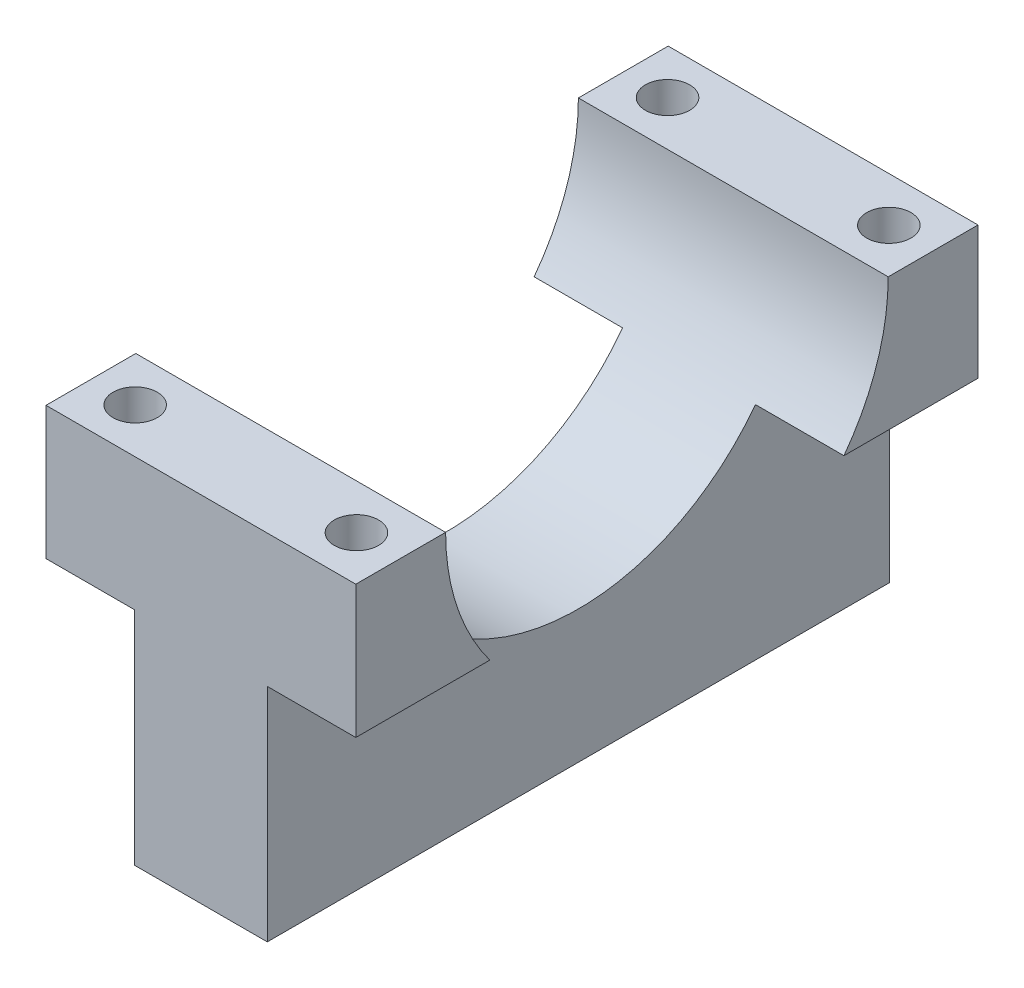
SolidWorks part; units mm, degrees
ref_plane "Front Plane" through (0, 0, 0) normal (0, 0, 1) x (1, 0, 0)
ref_plane "Top Plane" through (0, 0, 0) normal (0, 1, 0) x (1, 0, 0)
ref_plane "Right Plane" through (0, 0, 0) normal (1, 0, 0) x (0, 0, -1)
sketch "Sketch1" plane through (0, 0, 0) normal (0, 1, 0) x (1, 0, 0)
  line L0 (-58, -56) -> (58, -56)
  line L1 (-58, -56) -> (-58, 56)
  line L2 (58, -56) -> (58, 56)
  line L3 (-58, 56) -> (58, 56)
  line L4 (-58, -56) -> (58, 56) construction
  line L5 (58, -56) -> (-58, 56) construction
  line L6 (-63, -61) -> (-63, 61)
  line L7 (-63, 61) -> (63, 61)
  line L8 (63, -61) -> (63, 61)
  line L9 (-63, -61) -> (63, -61)
  point P1 (0, 0)
  dimension "D1" = 116
  dimension "D2" = 112
  dimension "D3" = 5
extrude "Boss-Extrude1" add sketch "Sketch1" along normal blind 15
fillet "Fillet1" radius 10 1 edges at (58, 7.5, -56)
fillet "Fillet2" radius 10 1 edges at (-58, 7.5, -56)
fillet "Fillet3" radius 10 1 edges at (-58, 7.5, 56)
fillet "Fillet4" radius 10 1 edges at (58, 7.5, 56)
sketch "Sketch4" plane through (0, 15, 0) normal (0, 1, 0) x (1, 0, 0)
  line L0 (-63, 61) -> (-63, 62.625)
  line L1 (-63, 62.625) -> (-61.675, 62.625)
  line L2 (-61.675, 62.625) -> (-61.675, 80.1975)
  line L3 (-61.675, 80.1975) -> (-57.925, 80.1975)
  line L4 (-65.425, 45.0525) -> (-65.425, 80.1975)
  line L5 (-65.425, 45.0525) -> (-57.925, 45.0525)
  line L6 (-65.425, 80.1975) -> (-57.925, 80.1975)
  line L7 (-57.925, 45.0525) -> (-57.925, 80.1975)
  line L8 (-65.425, 45.0525) -> (-57.925, 80.1975) construction
  line L9 (-65.425, 80.1975) -> (-57.925, 45.0525) construction
  dimension "D1" = 1.625
  dimension "D2" = 1.325
  dimension "D3" = 3.75
extrude "Boss-Extrude3" add sketch "Sketch4" along normal blind 49.75 and the other way up to surface contours L6 L4 L5 L7
sketch "Sketch5" plane through (-57.925, 0, 0) normal (1, 0, 0) x (0, 0, -1)
  line L0 (45.0525, 64.75) -> (80.1975, 64.75) construction
  circle A0 centre (62.625, 64.75) radius 12.5
  dimension "D1" = 25
extrude "Cut-Extrude1" cut sketch "Sketch5" against normal through all
ref_plane "Plane1" through (-61.675, 0, 0) normal (1, 0, 0) x (0, 0, -1)
sketch "Sketch6" plane through (-57.925, 0, 0) normal (1, 0, 0) x (0, 0, -1)
  line L0 (45.0525, 64.75) -> (50.125, 64.75)
  line L1 (45.0525, 64.75) -> (45.0525, 57.25)
  line L2 (45.0525, 0) -> (45.0525, 64.75) construction
  line L3 (45.0525, 57.25) -> (52.625, 57.25)
  arc A0 (50.125, 64.75) -> (75.125, 64.75) centre (62.625, 64.75) ccw construction
  arc A1 (52.625, 57.25) -> (50.125, 64.75) centre (62.625, 64.75) cw
  dimension "D1" = 7.5
extrude "Boss-Extrude4" add sketch "Sketch6" along normal blind 5
sketch "Sketch9" plane through (0, 64.75, 0) normal (0, 1, 0) x (1, 0, 0)
  line L0 (-52.925, 47.5887) -> (-55.425, 47.5887)
  line L1 (-52.925, 50.125) -> (-52.925, 45.0525) construction
  circle A0 centre (-55.425, 47.5887) radius 1.25
  dimension "D2" = 2.5
  dimension "D1" = 2.5
extrude "Cut-Extrude3" cut sketch "Sketch9" against normal through all
mirror "Mirror1" about plane through (-61.675, 0, 0) normal (1, 0, 0) of "Cut-Extrude3", "Boss-Extrude4"
ref_plane "Plane2" through (0, 0, -62.625) normal (0, 0, -1) x (-1, 0, 0)
mirror "Mirror2" about plane through (0, 0, -62.625) normal (0, 0, -1) of "Mirror1", "Boss-Extrude4", "Cut-Extrude3"
fillet "Fillet6" radius 17.5 1 edges at (-57.925, 7.5, -61)
fillet "Fillet7" radius 17.5 3 edges at (-52.7994, 15, -66.1256) (-54.6248, 15, -53.4908) (-57.925, 15, -62.8612)
fillet "Fillet8" radius 2 1 edges at (-63, 7.5, -45.0525)
fillet "Fillet9" radius 17.5 2 edges at (-63.5858, 15, -44.4667) (-61.5, 15, -45.0525)
fillet "Fillet10" radius 17.5 2 edges at (-57.925, 0, -79.3488) (-61.675, 0, -80.1975)
mirror "Mirror4" about plane through (0, 0, 0) normal (0, 0, 1) of "Mirror2", "Mirror1", "Cut-Extrude3", "Boss-Extrude4", "Cut-Extrude1", "Boss-Extrude3"
fillet "Fillet11" radius 2 1 edges at (-63, 7.5, 45.0525)
fillet "Fillet12" radius 17.5 2 edges at (-61.5, 15, 45.0525) (-63.5858, 15, 44.4667)
fillet "Fillet13" radius 17.5 1 edges at (-57.925, 7.5, 61)
fillet "Fillet14" radius 17.5 3 edges at (-54.6248, 15, 53.4908) (-57.925, 15, 62.8612) (-52.7994, 15, 66.1256)
fillet "Fillet15" radius 17.5 2 edges at (-57.925, 0, 79.3488) (-61.675, 0, 80.1975)
mirror "Mirror6" about plane through (0, 0, 0) normal (1, 0, 0) of "Mirror4", "Boss-Extrude3", "Boss-Extrude4", "Cut-Extrude3", "Mirror1", "Mirror2"
fillet "Fillet16" radius 2 1 edges at (63, 7.5, 45.0525)
fillet "Fillet17" radius 17.5 2 edges at (61.5, 15, 45.0525) (63.5858, 15, 44.4667)
fillet "Fillet18" radius 2 1 edges at (63, 7.5, -45.0525)
fillet "Fillet19" radius 17.5 2 edges at (61.5, 15, -45.0525) (63.5858, 15, -44.4667)
fillet "Fillet20" radius 17.5 1 edges at (57.925, 7.5, -61)
fillet "Fillet21" radius 17.5 3 edges at (54.6248, 15, -53.4908) (57.925, 15, -62.8612) (52.7994, 15, -66.1256)
fillet "Fillet22" radius 17.5 1 edges at (57.925, 7.5, 61)
fillet "Fillet23" radius 17.5 3 edges at (57.925, 15, 62.8612) (54.6248, 15, 53.4908) (52.7994, 15, 66.1256)
fillet "Fillet24" radius 17.5 2 edges at (57.925, 0, 79.3488) (61.675, 0, 80.1975)
fillet "Fillet25" radius 17.5 2 edges at (57.925, 0, -79.3488) (61.675, 0, -80.1975)
sketch "Sketch11" plane through (0, 0, 0) normal (0, -1, 0) x (-1, 0, 0)
  line L0 (0, 0) -> (0, 45.4)
  line L1 (0, 45.4) -> (-47.5, 45.4)
  line L3 (-8.25, 0) -> (8.25, 0) construction
  line L4 (0, 8.25) -> (0, -8.25) construction
  line L5 (-47.5, 45.4) -> (47.5, -45.4)
  line L6 (47.5, -45.4) -> (41.3679, -51.8158)
  line L7 (41.3679, -51.8158) -> (-58, 43.159)
  line L8 (-58, -45.0525) -> (-58, 45.0525) construction
  line L9 (41.3679, -51.8158) -> (45.5521, -56)
  line L10 (48, -56) -> (-48, -56) construction
  line L11 (47.5, -45.4) -> (53.7756, -39.1244)
  line L12 (-47.5, 45.4) -> (-41.2244, 51.6756)
  line L13 (-41.2244, 51.6756) -> (53.7756, -39.1244)
  line L14 (53.7756, -39.1244) -> (58, -43.1622)
  line L15 (58, 45.0525) -> (58, -45.0525) construction
  line L16 (-41.2244, 51.6756) -> (-45.7489, 56)
  line L17 (-48, 56) -> (48, 56) construction
  circle A0 centre (-47.5, 45.4) radius 5.875
  circle A1 centre (-47.5, 45.4) radius 8.875
  circle A4 centre (-47.5, -45.4) radius 8.875
  circle A5 centre (-47.5, -45.4) radius 5.875
  circle A6 centre (47.5, 45.4) radius 8.875
  circle A7 centre (47.5, 45.4) radius 5.875
  circle A8 centre (47.5, -45.4) radius 8.875
  circle A9 centre (47.5, -45.4) radius 5.875
  arc A10 (-58, 43.159) -> (-45.7489, 56) centre (-47.5646, 45.4677) cw
  arc A11 (45.5521, -56) -> (58, -43.1622) centre (48.4327, -46.3393) ccw
  line M27 (-58, -45.0525) -> (-58, 45.0525)
  line M28 (-58, 45.0525) -> (-57.925, 45.0525)
  line M29 (-57.925, 45.0525) -> (-57.925, 47.2224)
  arc M30 (-57.925, 47.2224) -> (-48, 56) centre (-48, 46) cw
  line M31 (-48, 56) -> (48, 56)
  line M35 (58, 45.0525) -> (58, -45.0525)
  line M36 (58, -45.0525) -> (57.925, -45.0525)
  line M37 (57.925, -45.0525) -> (57.925, -47.2224)
  arc M38 (57.925, -47.2224) -> (48, -56) centre (48, -46) cw
  line M39 (48, -56) -> (-48, -56)
  dimension "D3" = 11.75
  dimension "D4" = 17.75
  dimension "D1" = 45.4
  dimension "D2" = 47.5
extrude "Boss-Extrude5" add sketch "Sketch11" against normal blind 3.5 contours A8 L9 L14 M39 M38 M37 M36 M35 | A9 L6 A8 L11 | A9 L5 A8 L6 | A9 L11 L13 A8 L5 | A8 L5 A1 L7 | A8 L13 L0 L5 | A1 L5 L0 L13 L1 | A1 L1 L13 | L5 A1 L1 A0 | L1 A1 L12 A0 | A1 L5 A0 L12 L16 | A1 L16 L7 M31 M30 M29 M28 M27
mirror "Mirror7" about plane through (0, 0, 0) normal (0, 0, 1) of "Boss-Extrude5"
sketch "Sketch12" plane through (0, 0, 0) normal (0, -1, 0) x (-1, 0, 0)
  line L0 (0, 0) -> (-4, 0)
  line L1 (0, 0) -> (-0.0984, 56)
  line L2 (-45.7489, 56) -> (45.5521, 56) construction
  line L3 (4, -56.5079) -> (-4, -56.5079)
  line L4 (4, -56.5079) -> (4, 56.5079)
  line L5 (-4, -56.5079) -> (-4, 56.5079)
  line L6 (4, 56.5079) -> (-4, 56.5079)
  line L7 (4, -56.5079) -> (-4, 56.5079) construction
  line L8 (-4, -56.5079) -> (4, 56.5079) construction
  line M6 (-45.7489, -56) -> (-0.0016, -12.2753)
  line M7 (-0.0016, -12.2753) -> (41.3679, -51.8158)
  line M9 (45.5521, -56) -> (-45.7489, -56)
  line M13 (41.3679, 51.8158) -> (-0.0016, 12.2753)
  line M14 (-0.0016, 12.2753) -> (-45.7489, 56)
  line M15 (-45.7489, 56) -> (45.5521, 56)
  dimension "D1" = 4
extrude "Boss-Extrude6" add sketch "Sketch12" against normal up to surface (3.5 mm away) contours L4 L1 M13 M15 M14 | L5 L1 M14 M15 | L5 L4 M9 M7 M6 up to face at (47.5, 3.5, -51.275)
sketch "Sketch13" plane through (0, 0, 0) normal (0, -1, 0) x (-1, 0, 0)
  line L0 (0, 0) -> (0, 42.5)
  circle A0 centre (0, 42.5) radius 1.5
  dimension "D2" = 3
  dimension "D1" = 42.5
extrude "Cut-Extrude4" cut sketch "Sketch13" against normal through all
mirror "Mirror8" about plane through (0, 0, 0) normal (0, 0, 1) of "Cut-Extrude4"
ref_plane "Plane3" through (0, 44.75, 0) normal (0, 1, 0) x (1, 0, 0)
sketch "Sketch14" plane through (0, 44.75, 0) normal (0, 1, 0) x (1, 0, 0)
  circle A0 centre (0, 0) radius 158.4202
extrude "Cut-Extrude6" cut sketch "Sketch14" against normal through all
